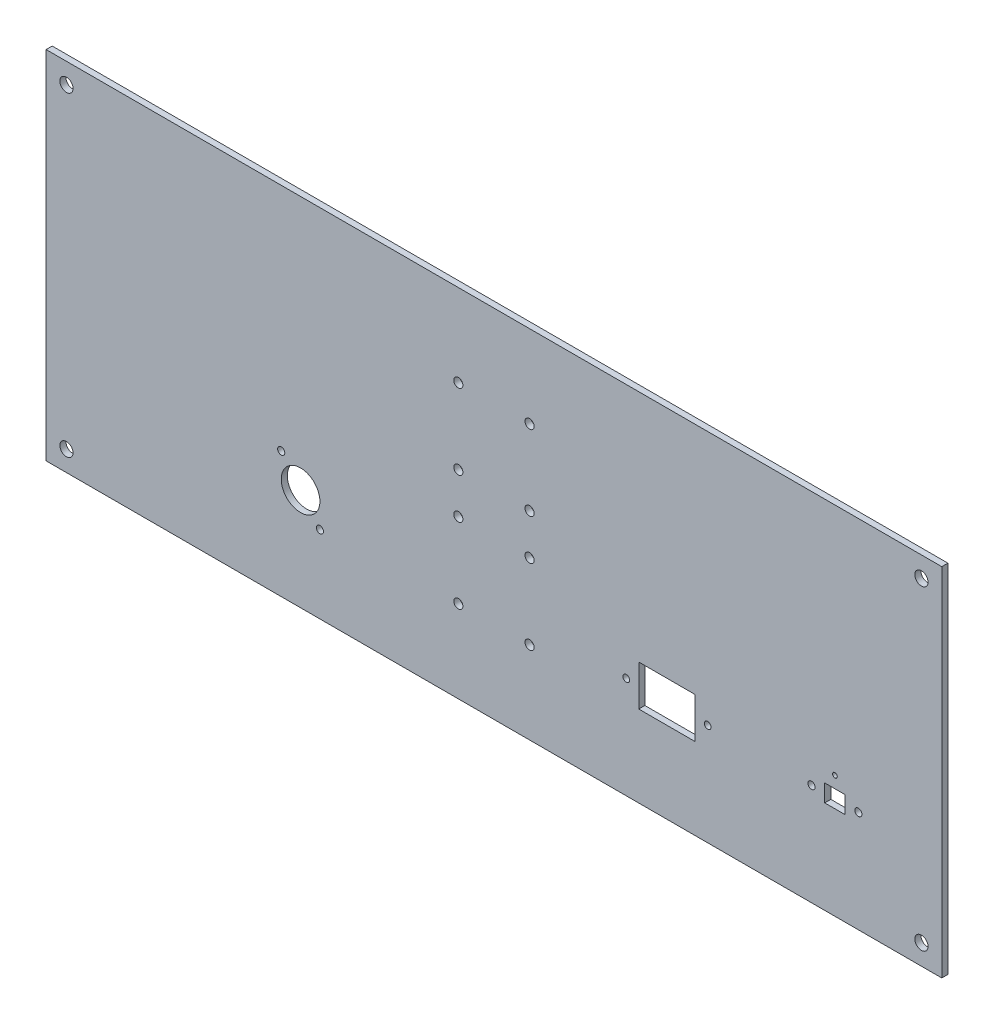
SolidWorks part; units mm, degrees
ref_plane "Front Plane" through (0, 0, 0) normal (0, 0, 1) x (1, 0, 0)
ref_plane "Top Plane" through (0, 0, 0) normal (0, 1, 0) x (1, 0, 0)
ref_plane "Right Plane" through (0, 0, 0) normal (1, 0, 0) x (0, 0, -1)
sketch "Sketch1" plane through (0, 0, 0) normal (0, 0, 1) x (1, 0, 0)
  line L0 (20, 155) -> (420, 155) construction
  line L1 (0, 0) -> (440, 0)
  line L2 (0, 0) -> (0, 175)
  line L3 (0, 175) -> (440, 175)
  line L4 (440, 0) -> (440, 175)
  line L5 (355, 155) -> (355, 20) construction
  line L6 (95, 155) -> (95, 20) construction
  line L7 (420, 20) -> (420, 155) construction
  line L8 (20, 20) -> (420, 20) construction
  line L9 (20, 20) -> (20, 155) construction
  line L10 (75, 155) -> (75, 20) construction
  line L11 (335, 155) -> (335, 20) construction
  line L12 (125, 155) -> (125, 20) construction
  line L13 (95, 50) -> (335, 50) construction
  line L14 (305, 155) -> (305, 20) construction
  line L15 (387.5, 20) -> (387.5, 155) construction
  line L16 (291.15, 40) -> (318.85, 40)
  line L17 (291.15, 40) -> (291.15, 60)
  line L18 (291.15, 60) -> (318.85, 60)
  line L19 (318.85, 40) -> (318.85, 60)
  line L20 (291.15, 40) -> (318.85, 60) construction
  line L21 (291.15, 60) -> (318.85, 40) construction
  line L22 (382.5, 45.75) -> (392.5, 45.75)
  line L23 (382.5, 45.75) -> (382.5, 54.25)
  line L24 (382.5, 54.25) -> (392.5, 54.25)
  line L25 (392.5, 45.75) -> (392.5, 54.25)
  line L26 (382.5, 45.75) -> (392.5, 54.25) construction
  line L27 (382.5, 54.25) -> (392.5, 45.75) construction
  line L28 (335, 50) -> (420, 50) construction
  line L29 (220, 20) -> (220, 155) construction
  line L30 (202.5, 155) -> (202.5, 20) construction
  line L31 (237.5, 155) -> (237.5, 20) construction
  line L32 (125, 87.5) -> (305, 87.5) construction
  circle A0 centre (125, 50) radius 9.5
  circle A1 centre (115.5, 62) radius 1.75
  circle A2 centre (134.5, 38) radius 1.75
  circle A3 centre (285, 50) radius 1.65
  circle A4 centre (325, 50) radius 1.65
  circle A5 centre (387.5, 60) radius 1.15
  circle A6 centre (376, 50) radius 1.75
  circle A7 centre (399, 50) radius 1.75
  circle A8 centre (10, 165) radius 3.25
  circle A9 centre (10, 10) radius 3.25
  circle A10 centre (430, 10) radius 3.25
  circle A11 centre (430, 165) radius 3.25
  circle A12 centre (202.5, 134.5) radius 2.25
  circle A13 centre (202.5, 97.5) radius 2.25
  circle A14 centre (237.5, 134.5) radius 2.25
  circle A15 centre (237.5, 97.5) radius 2.25
  circle A16 centre (237.5, 77.5) radius 2.25
  circle A17 centre (237.5, 40.5) radius 2.25
  circle A18 centre (202.5, 77.5) radius 2.25
  circle A19 centre (202.5, 40.5) radius 2.25
  point P24 (305, 50)
  point P37 (387.5, 50)
  point P83 (237.5, 127.9745)
  point P84 (237.5, 108.5309)
  point P85 (202.5, 108.5309)
  point P86 (237.5, 78.0579)
  point P87 (237.5, 63.0198)
  point P88 (202.5, 63.0198)
  point P89 (202.5, 79.5332)
  dimension "D9" = 30
  dimension "D13" = 20
  dimension "D12" = 20
  dimension "D14" = 3.3
  dimension "D15" = 3.3
  dimension "D20" = 5.75
  dimension "D21" = 2.3
  dimension "D22" = 23
  dimension "D23" = 11.5
  dimension "D24" = 3.5
  dimension "D25" = 3.5
  dimension "D30" = 6.5
  dimension "D33" = 10
  dimension "D51" = 3.5
  dimension "D52" = 19
  dimension "D54" = 4.5
  dimension "D59" = 37
  dimension "D1" = 55
  dimension "D2" = 65
  dimension "D3" = 440
  dimension "D4" = 20
  dimension "D5" = 20
  dimension "D6" = 240
  dimension "D7" = 30
  dimension "D8" = 30
  dimension "D10" = 20
  dimension "D11" = 27.7
  dimension "D16" = 8.5
  dimension "D17" = 10
  dimension "D18" = 32.5
  dimension "D19" = 32.5
  dimension "D26" = 50
  dimension "D27" = 125
  dimension "D28" = 135
  dimension "D29" = 52.5
  dimension "D31" = 10
  dimension "D32" = 10
  dimension "D34" = 10
  dimension "D35" = 10
  dimension "D36" = 10
  dimension "D37" = 10
  dimension "D38" = 10
  dimension "D39" = 12
  dimension "D40" = 12
  dimension "D41" = 9.5
  dimension "D42" = 9.5
  dimension "D43" = 38
  dimension "D44" = 62
  dimension "D45" = 134.5
  dimension "D46" = 115.5
  dimension "D47" = 10
  dimension "D48" = 4.25
  dimension "D49" = 13.85
  dimension "D50" = 10
  dimension "D53" = 220
  dimension "D55" = 17.5
  dimension "D56" = 35
  dimension "D57" = 87.5
  dimension "D58" = 175
  dimension "D60" = 37
  dimension "D61" = 10
  dimension "D62" = 10
  dimension "D63" = 10
  dimension "D64" = 10
  dimension "D65" = 37
  dimension "D66" = 37
  dimension "D67" = 40.5
  dimension "D68" = 77.5
  dimension "D69" = 97.5
  dimension "D70" = 134.5
  dimension "D71" = 202.5
  dimension "D72" = 237.5
extrude "Boss-Extrude1" add sketch "Sketch1" along normal blind 3
